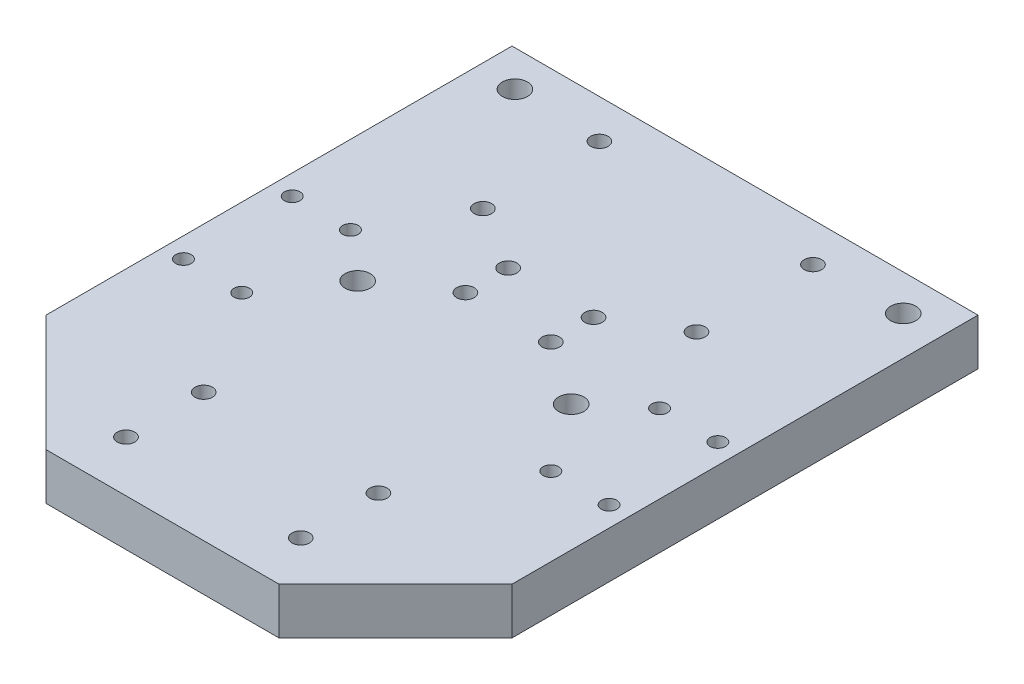
SolidWorks part; units mm, degrees
ref_plane "Alzado" through (0, 0, 0) normal (0, 0, 1) x (1, 0, 0)
ref_plane "Planta" through (0, 0, 0) normal (0, 1, 0) x (1, 0, 0)
ref_plane "Vista lateral" through (0, 0, 0) normal (1, 0, 0) x (0, 0, -1)
sketch "Croquis1" plane through (0, 0, 0) normal (1, 0, 0) x (0, 0, -1)
  line L0 (50, 0) -> (-250, 0)
  line L1 (-250, 0) -> (-250, -24)
  line L2 (-250, -24) -> (50, -24)
  line L3 (50, 0) -> (50, -24)
  dimension "D1" = 24
  dimension "D2" = 250
  dimension "D3" = 50
extrude "Saliente-Extruir1" add sketch "Croquis1" along normal blind 120 and the other way blind 120
sketch "Croquis2" plane through (0, 0, 0) normal (0, 1, 0) x (1, 0, 0)
  circle A0 centre (45, -183.8) radius 4.5
  circle A1 centre (45, -223.8) radius 4.5
  circle A2 centre (-45, -183.8) radius 4.5
  circle A3 centre (-45, -223.8) radius 4.5
  dimension "D1" = 9
  dimension "D2" = 9
  dimension "D3" = 9
  dimension "D4" = 9
extrude "Cortar-Extruir1" cut sketch "Croquis2" against normal up to next
sketch "Croquis3" plane through (0, -24, 0) normal (0, -1, 0) x (1, 0, 0)
  circle A0 centre (-45, 223.8) radius 7
  circle A1 centre (-45, 183.8) radius 7
  circle A2 centre (45, 223.8) radius 7
  circle A3 centre (45, 183.8) radius 7
  dimension "D1" = 14
  dimension "D2" = 14
  dimension "D3" = 14
  dimension "D4" = 14
extrude "Cortar-Extruir2" cut sketch "Croquis3" against normal blind 9
chamfer "Chaflán1" distance 60 angle 45 2 edges at (120, -12, 250) (-120, -12, 250)
sketch "Croquis4" plane through (0, 0, 0) normal (0, 1, 0) x (1, 0, 0)
  line L0 (-120, 50) -> (120, 50) construction
  circle A0 centre (100, 31.5) radius 6.5
  circle A1 centre (-100, 31.5) radius 6.5
  circle A2 centre (55, -94.5) radius 6.5
  circle A3 centre (-55, -94.5) radius 6.5
  dimension "D1" = 13
  dimension "D2" = 13
  dimension "D3" = 18.5
  dimension "D4" = 18.5
  dimension "D7" = 126
  dimension "D11" = 13
  dimension "D12" = 13
  dimension "D5" = 100
  dimension "D6" = 100
  dimension "D8" = 126
  dimension "D9" = 55
  dimension "D10" = 55
extrude "Cortar-Extruir3" cut sketch "Croquis4" against normal up to next
sketch "Croquis5" plane through (0, 0, 0) normal (0, 1, 0) x (1, 0, 0)
  circle A0 centre (79.6, -129.6) radius 4
  circle A1 centre (109.6, -129.6) radius 4
  circle A2 centre (109.6, -73.6) radius 4
  circle A3 centre (79.6, -73.6) radius 4
  circle A4 centre (-109.6, -129.6) radius 4
  circle A5 centre (-79.6, -129.6) radius 4
  circle A6 centre (-109.6, -73.6) radius 4
  circle A7 centre (-79.6, -73.6) radius 4
  dimension "D1" = 8
  dimension "D2" = 8
  dimension "D3" = 8
  dimension "D4" = 8
  dimension "D5" = 8
  dimension "D6" = 8
  dimension "D7" = 8
  dimension "D8" = 8
extrude "Cortar-Extruir4" cut sketch "Croquis5" against normal up to next
sketch "Croquis6" plane through (0, 0, 0) normal (0, 1, 0) x (1, 0, 0)
  circle A0 centre (-55, -30) radius 4.5
  circle A1 centre (-55, 30) radius 4.5
  circle A2 centre (55, 30) radius 4.5
  circle A3 centre (55, -30) radius 4.5
  dimension "D1" = 9
  dimension "D2" = 9
  dimension "D3" = 9
  dimension "D4" = 9
extrude "Cortar-Extruir5" cut sketch "Croquis6" against normal blind 30
sketch "Croquis7" plane through (0, -24, 0) normal (0, -1, 0) x (1, 0, 0)
  circle A0 centre (55, 30) radius 7
  circle A1 centre (55, -30) radius 7
  circle A2 centre (-55, 30) radius 7
  circle A3 centre (-55, -30) radius 7
  dimension "D1" = 14
  dimension "D2" = 14
  dimension "D3" = 14
  dimension "D4" = 14
extrude "Cortar-Extruir6" cut sketch "Croquis7" against normal blind 9
sketch "Croquis8" plane through (0, 0, 0) normal (0, 1, 0) x (1, 0, 0)
  circle A0 centre (-22, -50) radius 4.5
  circle A1 centre (-22, -72) radius 4.5
  circle A2 centre (22, -72) radius 4.5
  circle A3 centre (22, -50) radius 4.5
  dimension "D1" = 9
  dimension "D2" = 9
  dimension "D3" = 9
  dimension "D4" = 9
extrude "Cortar-Extruir7" cut sketch "Croquis8" against normal up to next
sketch "Croquis9" plane through (0, -24, 0) normal (0, -1, 0) x (1, 0, 0)
  circle A0 centre (22, 50) radius 7
  circle A1 centre (22, 72) radius 7
  circle A2 centre (-22, 72) radius 7
  circle A3 centre (-22, 50) radius 7
  dimension "D1" = 14
  dimension "D2" = 14
  dimension "D3" = 14
  dimension "D4" = 14
extrude "Cortar-Extruir8" cut sketch "Croquis9" against normal blind 9
